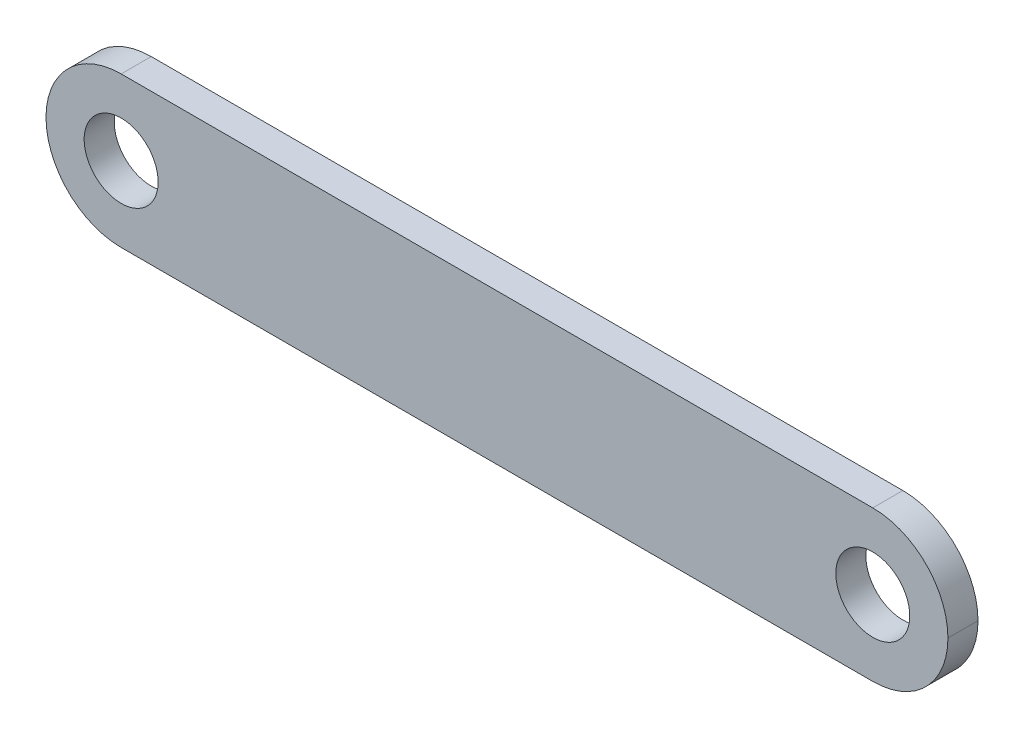
SolidWorks part; units mm, degrees
ref_plane "Front Plane" through (0, 0, 0) normal (0, 0, 1) x (1, 0, 0)
ref_plane "Top Plane" through (0, 0, 0) normal (0, 1, 0) x (1, 0, 0)
ref_plane "Right Plane" through (0, 0, 0) normal (1, 0, 0) x (0, 0, -1)
sketch "Sketch1" plane through (0, 0, 0) normal (0, 0, 1) x (1, 0, 0)
  line L1 (-76.2, -12.7) -> (76.2, -12.7)
  line L2 (-76.2, -12.7) -> (-76.2, 12.7)
  line L3 (-76.2, 12.7) -> (76.2, 12.7)
  line L4 (76.2, -12.7) -> (76.2, 12.7)
  line L5 (-76.2, -12.7) -> (76.2, 12.7) construction
  line L6 (-76.2, 12.7) -> (76.2, -12.7) construction
  point P0 (0, 0)
  dimension "D1" = 152.4
  dimension "D2" = 25.4
extrude "Boss-Extrude1" add sketch "Sketch1" along normal blind 5.08
sketch "Sketch3" plane through (0, 0, 5.08) normal (0, 0, 1) x (1, 0, 0)
  line L0 (-76.2, 0) -> (76.2, 0) construction
  line L1 (76.2, -12.7) -> (76.2, 12.7) construction
  line L2 (-63.5, 12.7) -> (-63.5, -12.7) construction
  line L3 (76.2, 12.7) -> (-76.2, 12.7) construction
  line L4 (-76.2, -12.7) -> (76.2, -12.7) construction
  line L5 (63.5, 12.7) -> (63.5, -12.7) construction
  line L7 (-76.2, 12.7) -> (-76.2, -12.7) construction
  point P6 (0, 0)
  dimension "D1" = 12.7
  dimension "D2" = 12.7
hole_wizard "Ø12.5 (12.5) Diameter Hole1" positions "Sketch4" profile "Sketch5" hole size "Ø12.5" standard "ANSI Metric" end condition through all
sketch "Sketch4" plane through (0, 0, 5.08) normal (0, 0, 1) x (1, 0, 0)
  line L0 (-63.5, 12.7) -> (-63.5, -12.7) construction
  line L1 (63.5, 12.7) -> (63.5, -12.7) construction
  point P0 (-63.5, 0)
  point P4 (63.5, 0)
sketch "Sketch5" plane through (-63.5, 0, 5.08) normal (1, 0, 0) x (0, -1, 0)
  line L0 (0, 0) -> (0, 5.08)
  line L1 (0, 5.08) -> (6.25, 5.08)
  line L2 (6.25, 5.08) -> (6.25, 0)
  line L5 (6.25, 0) -> (0, 0)
  line L11 (0, -6.35) -> (0, 107.95) construction
  dimension "Thru Hole Dia." = 12.5
  dimension "Thru Hole Depth" = 5.08
fillet "Fillet3" radius 12.7 4 edges at (-76.2, 12.7, 2.54) (-76.2, -12.7, 2.54) (76.2, -12.7, 2.54) (76.2, 12.7, 2.54)
